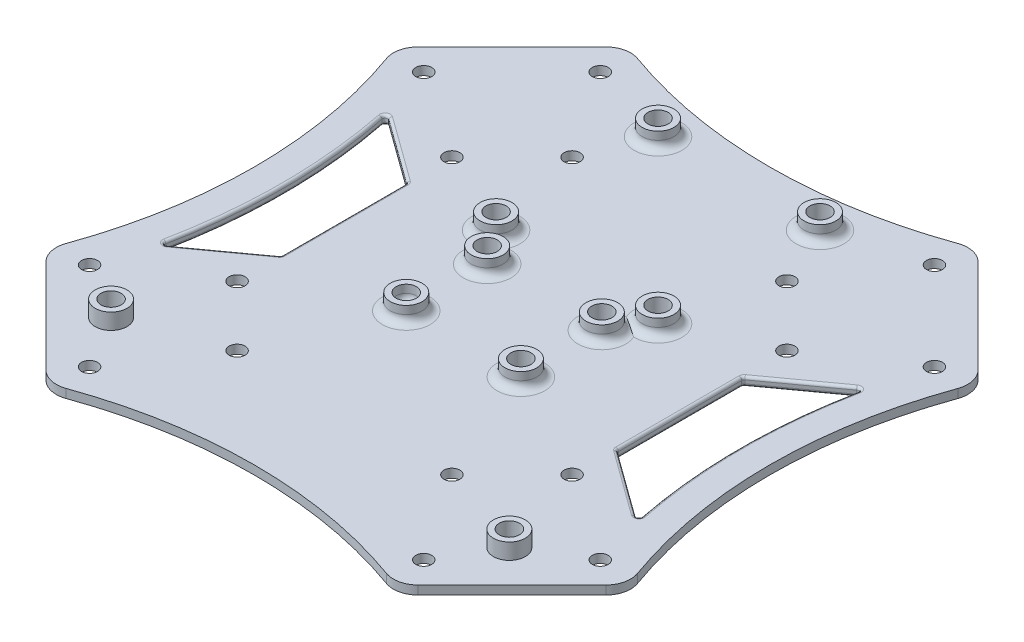
SolidWorks part; units mm, degrees
material "PLA"
ref_plane "Front Plane" through (0, 0, 0) normal (0, 0, 1) x (1, 0, 0)
ref_plane "Top Plane" through (0, 0, 0) normal (0, 1, 0) x (1, 0, 0)
ref_plane "Right Plane" through (0, 0, 0) normal (1, 0, 0) x (0, 0, -1)
sketch "Sketch1" plane through (0, 0, 0) normal (0, 1, 0) x (1, 0, 0)
  line L0 (-48.55, 0) -> (48.55, 0) construction
  line L1 (0, 48.55) -> (0, -48.55) construction
  line L2 (-30.1605, 53.8) -> (30.1605, 53.8) construction
  line L3 (0, 48.55) -> (0, 53.8) construction
  line L4 (-53.8, 30.1605) -> (-53.8, -30.1605) construction
  line L5 (-30.1605, -53.8) -> (30.1605, -53.8) construction
  line L6 (53.8, -30.1605) -> (53.8, 30.1605) construction
  line L7 (35.0464, 52.7056) -> (52.7056, 35.0464)
  line L8 (-52.7056, 35.0464) -> (-35.0464, 52.7056)
  line L9 (-52.7056, -35.0464) -> (-35.0464, -52.7056)
  line L10 (35.0464, -52.7056) -> (52.7056, -35.0464)
  line L11 (-43.876, -43.876) -> (43.876, 43.876) construction
  line L12 (-43.876, 43.876) -> (43.876, -43.876) construction
  line L13 (-31.7403, 54.075) -> (-31.7403, -54.075) construction
  line L14 (-31.7403, -54.075) -> (31.7403, -54.075) construction
  arc A0 (-30.1605, 53.8) -> (30.1605, 53.8) centre (0, 137.8088) ccw
  arc A1 (53.8, 30.1605) -> (53.8, -30.1605) centre (137.8088, 0) ccw
  arc A2 (30.1605, -53.8) -> (-30.1605, -53.8) centre (0, -137.8088) ccw
  arc A3 (-53.8, -30.1605) -> (-53.8, 30.1605) centre (-137.8088, 0) ccw
  arc A4 (-53.8, -30.1605) -> (-52.7056, -35.0464) centre (-49.3995, -31.7403) ccw
  arc A5 (-35.0464, -52.7056) -> (-30.1605, -53.8) centre (-31.7403, -49.3995) ccw
  arc A6 (30.1605, -53.8) -> (35.0464, -52.7056) centre (31.7403, -49.3995) ccw
  arc A7 (52.7056, -35.0464) -> (53.8, -30.1605) centre (49.3995, -31.7403) ccw
  arc A8 (53.8, 30.1605) -> (52.7056, 35.0464) centre (49.3995, 31.7403) ccw
  arc A9 (35.0464, 52.7056) -> (30.1605, 53.8) centre (31.7403, 49.3995) ccw
  arc A10 (-30.1605, 53.8) -> (-35.0464, 52.7056) centre (-31.7403, 49.3995) ccw
  arc A11 (-52.7056, 35.0464) -> (-53.8, 30.1605) centre (-49.3995, 31.7403) ccw
  point P2 (0, 0)
  point P6 (0, 0)
  point P34 (0, 0)
  dimension "D2" = 108.15
  dimension "D4" = 124.1
  dimension "D1" = 97.1
  dimension "D3" = 5.25
  dimension "D5" = 45
extrude "Boss-Extrude1" add sketch "Sketch1" along normal blind 0.825 and the other way blind 0.825
sketch "Sketch2" plane through (0, 0.825, 0) normal (0, 1, 0) x (1, 0, 0)
  line L0 (0, 30) -> (0, -30) construction
  line L1 (0, 40) -> (0, 30) construction
  line L2 (0, -30) -> (0, -40) construction
  line L3 (-15, 35) -> (15, 35) construction
  line L4 (15, 39) -> (15, 31)
  line L5 (-15, 39) -> (-15, 31)
  line L6 (-14, 40) -> (14, 40)
  line L7 (-14, 30) -> (14, 30)
  line L8 (-15, -35) -> (15, -35) construction
  line L9 (-15, -31) -> (-15, -39)
  line L10 (15, -31) -> (15, -39)
  line L11 (-14, -30) -> (14, -30)
  line L12 (-14, -40) -> (14, -40)
  line L13 (-18, 0) -> (18, 0) construction
  line L14 (-18, 0) -> (-27, 0) construction
  line L15 (18, 0) -> (27, 0) construction
  line L16 (-22.5, 9.5) -> (-22.5, -9.5) construction
  line L17 (22.5, 9.5) -> (22.5, -9.5) construction
  line L18 (-27, -9.5) -> (-27, 9.5)
  line L19 (-18, -9.5) -> (-18, 9.5)
  line L20 (18, -9.5) -> (18, 9.5)
  line L21 (27, -9.5) -> (27, 9.5)
  line L22 (-35, 0) -> (-27, 0) construction
  line L23 (-41, 0) -> (-35, 0) construction
  line L24 (27, 0) -> (35, 0) construction
  line L25 (35, 0) -> (41, 0) construction
  line L26 (-35, 11) -> (-35, -11)
  line L27 (-41, 11) -> (-41, -11)
  line L28 (-38, 11) -> (-38, -11) construction
  line L29 (35, 11) -> (35, -11)
  line L30 (41, 11) -> (41, -11)
  line L31 (38, 11) -> (38, -11) construction
  arc A0 (-14, 40) -> (-15, 39) centre (-14, 39) ccw
  arc A1 (15, 39) -> (14, 40) centre (14, 39) ccw
  arc A2 (-15, 31) -> (-14, 30) centre (-14, 31) ccw
  arc A3 (14, 30) -> (15, 31) centre (14, 31) ccw
  arc A4 (-14, -30) -> (-15, -31) centre (-14, -31) ccw
  arc A5 (15, -31) -> (14, -30) centre (14, -31) ccw
  arc A6 (14, -40) -> (15, -39) centre (14, -39) ccw
  arc A7 (-15, -39) -> (-14, -40) centre (-14, -39) ccw
  arc A8 (27, 9.5) -> (18, 9.5) centre (22.5, 9.5) ccw
  arc A9 (18, -9.5) -> (27, -9.5) centre (22.5, -9.5) ccw
  arc A10 (-27, -9.5) -> (-18, -9.5) centre (-22.5, -9.5) ccw
  arc A11 (-18, 9.5) -> (-27, 9.5) centre (-22.5, 9.5) ccw
  arc A12 (-35, 11) -> (-41, 11) centre (-38, 11) ccw
  arc A13 (-41, -11) -> (-35, -11) centre (-38, -11) ccw
  arc A14 (41, 11) -> (35, 11) centre (38, 11) ccw
  arc A15 (35, -11) -> (41, -11) centre (38, -11) ccw
  point P5 (0, 35)
  point P22 (0, -35)
  point P34 (-22.5, 0)
  point P36 (0, 0)
  point P45 (22.5, 0)
  point P64 (-38, 0)
  point P69 (38, 0)
  dimension "D6" = 30
  dimension "D8" = 36
  dimension "D13" = 8
  dimension "D18" = 22
  dimension "D1" = 60
  dimension "D2" = 10
  dimension "D3" = 10
  dimension "D4" = 30
  dimension "D5" = 8
  dimension "D7" = 8
  dimension "D9" = 9
  dimension "D10" = 9
  dimension "D11" = 19
  dimension "D12" = 19
  dimension "D14" = 8
  dimension "D15" = 6
  dimension "D16" = 6
  dimension "D17" = 22
extrude "Cut-Extrude1" [suppressed] cut sketch "Sketch2" against normal up to surface (1.65 mm away)
sketch "Sketch3" plane through (0, 0.825, 0) normal (0, 1, 0) x (1, 0, 0)
  line L0 (-48.0833, -31.4663) -> (-31.4663, -48.0833) construction
  line L1 (-52.7056, -35.0464) -> (-35.0464, -52.7056) construction
  line L2 (-39.7748, -39.7748) -> (-43.876, -43.876) construction
  line L3 (43.876, -43.876) -> (39.7748, -39.7748) construction
  line L4 (31.4663, -48.0833) -> (48.0833, -31.4663) construction
  line L5 (43.876, 43.876) -> (39.7748, 39.7748) construction
  line L6 (31.4663, 48.0833) -> (48.0833, 31.4663) construction
  line L7 (-43.876, 43.876) -> (-39.7748, 39.7748) construction
  line L8 (-31.4663, 48.0833) -> (-48.0833, 31.4663) construction
  line L9 (-35.0464, 52.7056) -> (-52.7056, 35.0464) construction
  line L10 (52.7056, 35.0464) -> (35.0464, 52.7056) construction
  line L11 (35.0464, -52.7056) -> (52.7056, -35.0464) construction
  line L12 (-31.5403, -20.2266) -> (-20.2266, -31.5403) construction
  line L13 (31.5403, -20.2266) -> (20.2266, -31.5403) construction
  line L14 (-31.5403, 20.2266) -> (-20.2266, 31.5403) construction
  line L15 (20.2266, 31.5403) -> (31.5403, 20.2266) construction
  line L16 (-25.8834, -25.8834) -> (-39.7748, -39.7748) construction
  line L17 (-39.7748, 39.7748) -> (-25.8834, 25.8834) construction
  line L18 (39.7748, 39.7748) -> (25.8834, 25.8834) construction
  line L19 (25.8834, -25.8834) -> (39.7748, -39.7748) construction
  line L20 (-20.2266, -31.5403) -> (-31.4663, -48.0833) construction
  line L21 (-31.5403, -20.2266) -> (-48.0833, -31.4663) construction
  circle A0 centre (-48.0833, -31.4663) radius 1.5
  circle A1 centre (-31.4663, -48.0833) radius 1.5
  circle A2 centre (31.4663, -48.0833) radius 1.5
  circle A3 centre (48.0833, -31.4663) radius 1.5
  circle A4 centre (48.0833, 31.4663) radius 1.5
  circle A5 centre (31.4663, 48.0833) radius 1.5
  circle A6 centre (-31.4663, 48.0833) radius 1.5
  circle A7 centre (-48.0833, 31.4663) radius 1.5
  circle A8 centre (-31.5403, -20.2266) radius 1.5
  circle A9 centre (-20.2266, -31.5403) radius 1.5
  circle A10 centre (-31.5403, 20.2266) radius 1.5
  circle A11 centre (-20.2266, 31.5403) radius 1.5
  circle A12 centre (20.2266, 31.5403) radius 1.5
  circle A13 centre (31.5403, 20.2266) radius 1.5
  circle A14 centre (31.5403, -20.2266) radius 1.5
  circle A15 centre (20.2266, -31.5403) radius 1.5
  dimension "D3" = 3
  dimension "D4" = 20
  dimension "D1" = 23.5
  dimension "D2" = 5.8
  dimension "D5" = 16
extrude "Cut-Extrude2" cut sketch "Sketch3" against normal up to surface (1.65 mm away) up to face at (0, -0.825, 0)
sketch "Sketch4" [suppressed] plane through (0, 0.825, 0) normal (0, 1, 0) x (1, 0, 0)
  line L0 (15.25, -39) -> (15.25, -31)
  line L1 (-15.25, -39) -> (-15.25, -31)
  line L2 (-14, -29.75) -> (14, -29.75)
  line L3 (-14, -40.25) -> (14, -40.25)
  line L4 (15, -39) -> (15, -31) construction
  line L5 (17.05, -39) -> (17.05, -31)
  line L6 (-14, -27.95) -> (14, -27.95)
  line L7 (-17.05, -39) -> (-17.05, -31)
  line L8 (-14, -42.05) -> (14, -42.05)
  line L9 (-14, 29.75) -> (14, 29.75)
  line L10 (-15.25, 31) -> (-15.25, 39)
  line L11 (-14, 40.25) -> (14, 40.25)
  line L12 (15.25, 39) -> (15.25, 31)
  line L13 (15, 31) -> (15, 39) construction
  line L14 (17.05, 39) -> (17.05, 31)
  line L15 (-14, 27.95) -> (14, 27.95)
  line L16 (-17.05, 31) -> (-17.05, 39)
  line L17 (-14, 42.05) -> (14, 42.05)
  line L18 (34.8696, -52.5288) -> (52.5288, -34.8696)
  line L19 (35.0464, -52.7056) -> (52.7056, -35.0464) construction
  line L20 (34.8696, 52.5288) -> (52.5288, 34.8696)
  line L21 (52.7056, 35.0464) -> (35.0464, 52.7056) construction
  line L22 (-52.5288, 34.8696) -> (-34.8696, 52.5288)
  line L23 (-35.0464, 52.7056) -> (-52.7056, 35.0464) construction
  line L24 (-52.5288, -34.8696) -> (-34.8696, -52.5288)
  line L25 (-52.7056, -35.0464) -> (-35.0464, -52.7056) construction
  line L26 (-51.256, 33.5968) -> (-33.5968, 51.256)
  line L27 (33.5968, 51.256) -> (51.256, 33.5968)
  line L28 (33.5968, -51.256) -> (51.256, -33.5968)
  line L29 (-51.256, -33.5968) -> (-33.5968, -51.256)
  line L30 (-31.4663, -45.8333) -> (-31.4663, -46.5833) construction
  line L31 (-29.5177, -46.9583) -> (-31.4663, -45.8333) construction
  line L32 (-31.4663, -45.8333) -> (-33.4148, -46.9583) construction
  line L33 (-33.4148, -46.9583) -> (-33.4148, -49.2083) construction
  line L34 (-33.4148, -49.2083) -> (-31.4663, -50.3333) construction
  line L35 (-31.4663, -50.3333) -> (-29.5177, -49.2083) construction
  line L36 (-29.5177, -49.2083) -> (-29.5177, -46.9583) construction
  line L37 (-31.4663, -45.8333) -> (-31.4663, -45.0833) construction
  line L39 (-48.0833, -29.2163) -> (-50.0318, -30.3413) construction
  line L40 (-50.0318, -30.3413) -> (-50.0318, -32.5913) construction
  line L41 (-50.0318, -32.5913) -> (-48.0833, -33.7163) construction
  line L42 (-48.0833, -33.7163) -> (-46.1347, -32.5913) construction
  line L43 (-46.1347, -32.5913) -> (-46.1347, -30.3413) construction
  line L44 (-46.1347, -30.3413) -> (-48.0833, -29.2163) construction
  line L45 (-31.5403, -17.9766) -> (-33.4888, -19.1016) construction
  line L46 (-33.4888, -19.1016) -> (-33.4888, -21.3516) construction
  line L47 (-33.4888, -21.3516) -> (-31.5403, -22.4766) construction
  line L48 (-31.5403, -22.4766) -> (-29.5917, -21.3516) construction
  line L49 (-29.5917, -21.3516) -> (-29.5917, -19.1016) construction
  line L50 (-29.5917, -19.1016) -> (-31.5403, -17.9766) construction
  line L51 (-20.2266, -29.2903) -> (-22.1751, -30.4153) construction
  line L52 (-22.1751, -30.4153) -> (-22.1751, -32.6653) construction
  line L53 (-22.1751, -32.6653) -> (-20.2266, -33.7903) construction
  line L54 (-20.2266, -33.7903) -> (-18.278, -32.6653) construction
  line L55 (-18.278, -32.6653) -> (-18.278, -30.4153) construction
  line L56 (-18.278, -30.4153) -> (-20.2266, -29.2903) construction
  line L57 (20.2266, 33.7903) -> (18.278, 32.6653) construction
  line L58 (18.278, 32.6653) -> (18.278, 30.4153) construction
  line L59 (18.278, 30.4153) -> (20.2266, 29.2903) construction
  line L60 (20.2266, 29.2903) -> (22.1751, 30.4153) construction
  line L61 (22.1751, 30.4153) -> (22.1751, 32.6653) construction
  line L62 (22.1751, 32.6653) -> (20.2266, 33.7903) construction
  line L63 (31.5403, 22.4766) -> (29.5917, 21.3516) construction
  line L64 (29.5917, 21.3516) -> (29.5917, 19.1016) construction
  line L65 (29.5917, 19.1016) -> (31.5403, 17.9766) construction
  line L66 (31.5403, 17.9766) -> (33.4888, 19.1016) construction
  line L67 (33.4888, 19.1016) -> (33.4888, 21.3516) construction
  line L68 (33.4888, 21.3516) -> (31.5403, 22.4766) construction
  line L69 (48.0833, 33.7163) -> (46.1347, 32.5913) construction
  line L70 (46.1347, 32.5913) -> (46.1347, 30.3413) construction
  line L71 (46.1347, 30.3413) -> (48.0833, 29.2163) construction
  line L72 (48.0833, 29.2163) -> (50.0318, 30.3413) construction
  line L73 (50.0318, 30.3413) -> (50.0318, 32.5913) construction
  line L74 (50.0318, 32.5913) -> (48.0833, 33.7163) construction
  line L75 (31.4663, 50.3333) -> (29.5177, 49.2083) construction
  line L76 (29.5177, 49.2083) -> (29.5177, 46.9583) construction
  line L77 (29.5177, 46.9583) -> (31.4663, 45.8333) construction
  line L78 (31.4663, 45.8333) -> (33.4148, 46.9583) construction
  line L79 (33.4148, 46.9583) -> (33.4148, 49.2083) construction
  line L80 (33.4148, 49.2083) -> (31.4663, 50.3333) construction
  line L81 (-50.3333, 31.4663) -> (-49.2083, 29.5177) construction
  line L82 (-49.2083, 29.5177) -> (-46.9583, 29.5177) construction
  line L83 (-46.9583, 29.5177) -> (-45.8333, 31.4663) construction
  line L84 (-45.8333, 31.4663) -> (-46.9583, 33.4148) construction
  line L85 (-46.9583, 33.4148) -> (-49.2083, 33.4148) construction
  line L86 (-49.2083, 33.4148) -> (-50.3333, 31.4663) construction
  line L87 (-33.7903, 20.2266) -> (-32.6653, 18.278) construction
  line L88 (-32.6653, 18.278) -> (-30.4153, 18.278) construction
  line L89 (-30.4153, 18.278) -> (-29.2903, 20.2266) construction
  line L90 (-29.2903, 20.2266) -> (-30.4153, 22.1751) construction
  line L91 (-30.4153, 22.1751) -> (-32.6653, 22.1751) construction
  line L92 (-32.6653, 22.1751) -> (-33.7903, 20.2266) construction
  line L93 (-22.4766, 31.5403) -> (-21.3516, 29.5917) construction
  line L94 (-21.3516, 29.5917) -> (-19.1016, 29.5917) construction
  line L95 (-19.1016, 29.5917) -> (-17.9766, 31.5403) construction
  line L96 (-17.9766, 31.5403) -> (-19.1016, 33.4888) construction
  line L97 (-19.1016, 33.4888) -> (-21.3516, 33.4888) construction
  line L98 (-21.3516, 33.4888) -> (-22.4766, 31.5403) construction
  line L99 (-29.2163, 48.0833) -> (-30.3413, 50.0318) construction
  line L100 (-30.3413, 50.0318) -> (-32.5913, 50.0318) construction
  line L101 (-32.5913, 50.0318) -> (-33.7163, 48.0833) construction
  line L102 (-33.7163, 48.0833) -> (-32.5913, 46.1347) construction
  line L103 (-32.5913, 46.1347) -> (-30.3413, 46.1347) construction
  line L104 (-30.3413, 46.1347) -> (-29.2163, 48.0833) construction
  line L105 (22.4766, -31.5403) -> (21.3516, -29.5917) construction
  line L106 (21.3516, -29.5917) -> (19.1016, -29.5917) construction
  line L107 (19.1016, -29.5917) -> (17.9766, -31.5403) construction
  line L108 (17.9766, -31.5403) -> (19.1016, -33.4888) construction
  line L109 (19.1016, -33.4888) -> (21.3516, -33.4888) construction
  line L110 (21.3516, -33.4888) -> (22.4766, -31.5403) construction
  line L111 (33.7903, -20.2266) -> (32.6653, -18.278) construction
  line L112 (32.6653, -18.278) -> (30.4153, -18.278) construction
  line L113 (30.4153, -18.278) -> (29.2903, -20.2266) construction
  line L114 (29.2903, -20.2266) -> (30.4153, -22.1751) construction
  line L115 (30.4153, -22.1751) -> (32.6653, -22.1751) construction
  line L116 (32.6653, -22.1751) -> (33.7903, -20.2266) construction
  line L117 (33.7163, -48.0833) -> (32.5913, -46.1347) construction
  line L118 (32.5913, -46.1347) -> (30.3413, -46.1347) construction
  line L119 (30.3413, -46.1347) -> (29.2163, -48.0833) construction
  line L120 (29.2163, -48.0833) -> (30.3413, -50.0318) construction
  line L121 (30.3413, -50.0318) -> (32.5913, -50.0318) construction
  line L122 (32.5913, -50.0318) -> (33.7163, -48.0833) construction
  line L123 (50.3333, -31.4663) -> (49.2083, -29.5177) construction
  line L124 (49.2083, -29.5177) -> (46.9583, -29.5177) construction
  line L125 (46.9583, -29.5177) -> (45.8333, -31.4663) construction
  line L126 (45.8333, -31.4663) -> (46.9583, -33.4148) construction
  line L127 (46.9583, -33.4148) -> (49.2083, -33.4148) construction
  line L128 (49.2083, -33.4148) -> (50.3333, -31.4663) construction
  arc A0 (-14, -29.75) -> (-15.25, -31) centre (-14, -31) ccw
  arc A1 (15.25, -31) -> (14, -29.75) centre (14, -31) ccw
  arc A2 (-15.25, -39) -> (-14, -40.25) centre (-14, -39) ccw
  arc A3 (14, -40.25) -> (15.25, -39) centre (14, -39) ccw
  arc A4 (14, -40) -> (15, -39) centre (14, -39) ccw construction
  arc A5 (15, -31) -> (14, -30) centre (14, -31) ccw construction
  arc A6 (-14, -30) -> (-15, -31) centre (-14, -31) ccw construction
  arc A7 (-15, -39) -> (-14, -40) centre (-14, -39) ccw construction
  arc A8 (17.05, -31) -> (14, -27.95) centre (14, -31) ccw
  arc A9 (-14, -27.95) -> (-17.05, -31) centre (-14, -31) ccw
  arc A10 (-17.05, -39) -> (-14, -42.05) centre (-14, -39) ccw
  arc A11 (14, -42.05) -> (17.05, -39) centre (14, -39) ccw
  arc A12 (-15.25, 31) -> (-14, 29.75) centre (-14, 31) ccw
  arc A13 (-14, 40.25) -> (-15.25, 39) centre (-14, 39) ccw
  arc A14 (15.25, 39) -> (14, 40.25) centre (14, 39) ccw
  arc A15 (14, 29.75) -> (15.25, 31) centre (14, 31) ccw
  arc A16 (14, 30) -> (15, 31) centre (14, 31) ccw construction
  arc A17 (15, 39) -> (14, 40) centre (14, 39) ccw construction
  arc A18 (-14, 40) -> (-15, 39) centre (-14, 39) ccw construction
  arc A19 (-15, 31) -> (-14, 30) centre (-14, 31) ccw construction
  arc A20 (14, 27.95) -> (17.05, 31) centre (14, 31) ccw
  arc A21 (-17.05, 31) -> (-14, 27.95) centre (-14, 31) ccw
  arc A22 (-14, 42.05) -> (-17.05, 39) centre (-14, 39) ccw
  arc A23 (17.05, 39) -> (14, 42.05) centre (14, 39) ccw
  arc A24 (30.245, -53.5647) -> (-30.245, -53.5647) centre (0, -137.8088) ccw
  arc A25 (30.1605, -53.8) -> (-30.1605, -53.8) centre (0, -137.8088) ccw construction
  arc A26 (-53.5647, -30.245) -> (-53.5647, 30.245) centre (-137.8088, 0) ccw
  arc A27 (-30.245, 53.5647) -> (30.245, 53.5647) centre (0, 137.8088) ccw
  arc A28 (53.5647, 30.245) -> (53.5647, -30.245) centre (137.8088, 0) ccw
  arc A29 (53.8, 30.1605) -> (53.8, -30.1605) centre (137.8088, 0) ccw construction
  arc A30 (-30.1605, 53.8) -> (30.1605, 53.8) centre (0, 137.8088) ccw construction
  arc A31 (-53.8, -30.1605) -> (-53.8, 30.1605) centre (-137.8088, 0) ccw construction
  arc A32 (34.8696, 52.5288) -> (30.245, 53.5647) centre (31.7403, 49.3995) ccw
  arc A33 (35.0464, 52.7056) -> (30.1605, 53.8) centre (31.7403, 49.3995) ccw construction
  arc A34 (53.5647, 30.245) -> (52.5288, 34.8696) centre (49.3995, 31.7403) ccw
  arc A35 (53.8, 30.1605) -> (52.7056, 35.0464) centre (49.3995, 31.7403) ccw construction
  arc A36 (52.5288, -34.8696) -> (53.5647, -30.245) centre (49.3995, -31.7403) ccw
  arc A37 (52.7056, -35.0464) -> (53.8, -30.1605) centre (49.3995, -31.7403) ccw construction
  arc A38 (30.245, -53.5647) -> (34.8696, -52.5288) centre (31.7403, -49.3995) ccw
  arc A39 (30.1605, -53.8) -> (35.0464, -52.7056) centre (31.7403, -49.3995) ccw construction
  arc A40 (-34.8696, -52.5288) -> (-30.245, -53.5647) centre (-31.7403, -49.3995) ccw
  arc A41 (-35.0464, -52.7056) -> (-30.1605, -53.8) centre (-31.7403, -49.3995) ccw construction
  arc A42 (-53.5647, -30.245) -> (-52.5288, -34.8696) centre (-49.3995, -31.7403) ccw
  arc A43 (-53.8, -30.1605) -> (-52.7056, -35.0464) centre (-49.3995, -31.7403) ccw construction
  arc A44 (-52.5288, 34.8696) -> (-53.5647, 30.245) centre (-49.3995, 31.7403) ccw
  arc A45 (-52.7056, 35.0464) -> (-53.8, 30.1605) centre (-49.3995, 31.7403) ccw construction
  arc A46 (-30.245, 53.5647) -> (-34.8696, 52.5288) centre (-31.7403, 49.3995) ccw
  arc A47 (-30.1605, 53.8) -> (-35.0464, 52.7056) centre (-31.7403, 49.3995) ccw construction
  arc A48 (-51.8706, -30.8532) -> (-51.8706, 30.8532) centre (-137.8088, 0) ccw
  arc A49 (-51.256, 33.5968) -> (-51.8706, 30.8532) centre (-49.3995, 31.7403) ccw
  arc A50 (-30.8532, 51.8706) -> (-33.5968, 51.256) centre (-31.7403, 49.3995) ccw
  arc A51 (-30.8532, 51.8706) -> (30.8532, 51.8706) centre (0, 137.8088) ccw
  arc A52 (33.5968, 51.256) -> (30.8532, 51.8706) centre (31.7403, 49.3995) ccw
  arc A53 (51.8706, 30.8532) -> (51.256, 33.5968) centre (49.3995, 31.7403) ccw
  arc A54 (51.8706, 30.8532) -> (51.8706, -30.8532) centre (137.8088, 0) ccw
  arc A55 (51.256, -33.5968) -> (51.8706, -30.8532) centre (49.3995, -31.7403) ccw
  arc A56 (30.8532, -51.8706) -> (33.5968, -51.256) centre (31.7403, -49.3995) ccw
  arc A57 (30.8532, -51.8706) -> (-30.8532, -51.8706) centre (0, -137.8088) ccw
  arc A58 (-33.5968, -51.256) -> (-30.8532, -51.8706) centre (-31.7403, -49.3995) ccw
  arc A59 (-51.8706, -30.8532) -> (-51.256, -33.5968) centre (-49.3995, -31.7403) ccw
  circle A60 centre (-31.4663, -48.0833) radius 3
  circle A61 centre (-48.0833, -31.4663) radius 3
  circle A62 centre (-31.5403, -20.2266) radius 3
  circle A63 centre (-20.2266, -31.5403) radius 3
  circle A64 centre (-48.0833, 31.4663) radius 3
  circle A65 centre (-31.5403, 20.2266) radius 3
  circle A66 centre (-20.2266, 31.5403) radius 3
  circle A67 centre (-31.4663, 48.0833) radius 3
  circle A68 centre (20.2266, 31.5403) radius 3
  circle A69 centre (31.4663, 48.0833) radius 3
  circle A70 centre (48.0833, 31.4663) radius 3
  circle A71 centre (31.5403, 20.2266) radius 3
  circle A72 centre (20.2266, -31.5403) radius 3
  circle A73 centre (31.5403, -20.2266) radius 3
  circle A74 centre (48.0833, -31.4663) radius 3
  circle A75 centre (31.4663, -48.0833) radius 3
  circle A76 centre (-31.4663, -48.0833) radius 1.5 construction
  circle A77 centre (-48.0833, -31.4663) radius 1.5 construction
  circle A78 centre (-31.5403, -20.2266) radius 1.5 construction
  circle A79 centre (-20.2266, -31.5403) radius 1.5 construction
  circle A80 centre (20.2266, -31.5403) radius 1.5 construction
  circle A81 centre (31.4663, -48.0833) radius 1.5 construction
  circle A82 centre (48.0833, -31.4663) radius 1.5 construction
  circle A83 centre (31.5403, -20.2266) radius 1.5 construction
  circle A84 centre (48.0833, 31.4663) radius 1.5 construction
  circle A85 centre (31.5403, 20.2266) radius 1.5 construction
  circle A86 centre (20.2266, 31.5403) radius 1.5 construction
  circle A87 centre (31.4663, 48.0833) radius 1.5 construction
  circle A88 centre (-20.2266, 31.5403) radius 1.5 construction
  circle A89 centre (-31.5403, 20.2266) radius 1.5 construction
  circle A90 centre (-48.0833, 31.4663) radius 1.5 construction
  circle A91 centre (-31.4663, 48.0833) radius 1.5 construction
  circle A92 centre (-48.0833, -31.4663) radius 1.5
  circle A93 centre (-31.4663, -48.0833) radius 1.5
  circle A94 centre (-20.2266, -31.5403) radius 1.5
  circle A95 centre (-31.5403, -20.2266) radius 1.5
  circle A96 centre (-48.0833, 31.4663) radius 1.5
  circle A97 centre (-31.5403, 20.2266) radius 1.5
  circle A98 centre (-20.2266, 31.5403) radius 1.5
  circle A99 centre (-31.4663, 48.0833) radius 1.5
  circle A100 centre (20.2266, 31.5403) radius 1.5
  circle A101 centre (31.4663, 48.0833) radius 1.5
  circle A102 centre (48.0833, 31.4663) radius 1.5
  circle A103 centre (31.5403, 20.2266) radius 1.5
  circle A104 centre (31.5403, -20.2266) radius 1.5
  circle A105 centre (20.2266, -31.5403) radius 1.5
  circle A106 centre (48.0833, -31.4663) radius 1.5
  circle A107 centre (31.4663, -48.0833) radius 1.5
  circle A108 centre (-31.4663, -48.0833) radius 1.9486 construction
  circle A109 centre (-48.0833, -31.4663) radius 1.9486 construction
  circle A110 centre (-31.5403, -20.2266) radius 1.9486 construction
  circle A111 centre (-20.2266, -31.5403) radius 1.9486 construction
  circle A112 centre (-31.4663, -50.3333) radius 0.25
  circle A113 centre (-29.5177, -49.2083) radius 0.25
  circle A114 centre (-29.5177, -46.9583) radius 0.25
  circle A115 centre (-31.4663, -45.8333) radius 0.25
  circle A116 centre (-33.4148, -46.9583) radius 0.25
  circle A117 centre (-33.4148, -49.2083) radius 0.25
  circle A118 centre (-48.0833, -33.7163) radius 0.25
  circle A119 centre (-46.1347, -32.5913) radius 0.25
  circle A120 centre (-46.1347, -30.3413) radius 0.25
  circle A121 centre (-48.0833, -29.2163) radius 0.25
  circle A122 centre (-50.0318, -30.3413) radius 0.25
  circle A123 centre (-50.0318, -32.5913) radius 0.25
  circle A124 centre (-31.5403, -22.4766) radius 0.25
  circle A125 centre (-29.5917, -21.3516) radius 0.25
  circle A126 centre (-29.5917, -19.1016) radius 0.25
  circle A127 centre (-31.5403, -17.9766) radius 0.25
  circle A128 centre (-33.4888, -19.1016) radius 0.25
  circle A129 centre (-33.4888, -21.3516) radius 0.25
  circle A130 centre (-20.2266, -33.7903) radius 0.25
  circle A131 centre (-18.278, -32.6653) radius 0.25
  circle A132 centre (-18.278, -30.4153) radius 0.25
  circle A133 centre (-20.2266, -29.2903) radius 0.25
  circle A134 centre (-22.1751, -30.4153) radius 0.25
  circle A135 centre (-22.1751, -32.6653) radius 0.25
  circle A136 centre (20.2266, 31.5403) radius 1.9486 construction
  circle A137 centre (31.5403, 20.2266) radius 1.9486 construction
  circle A138 centre (48.0833, 31.4663) radius 1.9486 construction
  circle A139 centre (31.4663, 48.0833) radius 1.9486 construction
  circle A140 centre (20.2266, 29.2903) radius 0.25
  circle A141 centre (22.1751, 30.4153) radius 0.25
  circle A142 centre (22.1751, 32.6653) radius 0.25
  circle A143 centre (18.278, 30.4153) radius 0.25
  circle A144 centre (18.278, 32.6653) radius 0.25
  circle A145 centre (20.2266, 33.7903) radius 0.25
  circle A146 centre (31.4663, 45.8333) radius 0.25
  circle A147 centre (29.5177, 46.9583) radius 0.25
  circle A148 centre (29.5177, 49.2083) radius 0.25
  circle A149 centre (31.4663, 50.3333) radius 0.25
  circle A150 centre (33.4148, 49.2083) radius 0.25
  circle A151 centre (33.4148, 46.9583) radius 0.25
  circle A152 centre (29.5917, 21.3516) radius 0.25
  circle A153 centre (29.5917, 19.1016) radius 0.25
  circle A154 centre (31.5403, 17.9766) radius 0.25
  circle A155 centre (33.4888, 19.1016) radius 0.25
  circle A156 centre (33.4888, 21.3516) radius 0.25
  circle A157 centre (31.5403, 22.4766) radius 0.25
  circle A158 centre (48.0833, 29.2163) radius 0.25
  circle A159 centre (46.1347, 30.3413) radius 0.25
  circle A160 centre (50.0318, 30.3413) radius 0.25
  circle A161 centre (50.0318, 32.5913) radius 0.25
  circle A162 centre (48.0833, 33.7163) radius 0.25
  circle A163 centre (46.1347, 32.5913) radius 0.25
  circle A164 centre (-48.0833, 31.4663) radius 1.9486 construction
  circle A165 centre (-31.5403, 20.2266) radius 1.9486 construction
  circle A166 centre (-20.2266, 31.5403) radius 1.9486 construction
  circle A167 centre (-31.4663, 48.0833) radius 1.9486 construction
  circle A168 centre (-46.9583, 29.5177) radius 0.25
  circle A169 centre (-45.8333, 31.4663) radius 0.25
  circle A170 centre (-46.9583, 33.4148) radius 0.25
  circle A171 centre (-49.2083, 33.4148) radius 0.25
  circle A172 centre (-50.3333, 31.4663) radius 0.25
  circle A173 centre (-49.2083, 29.5177) radius 0.25
  circle A174 centre (-32.6653, 18.278) radius 0.25
  circle A175 centre (-33.7903, 20.2266) radius 0.25
  circle A176 centre (-32.6653, 22.1751) radius 0.25
  circle A177 centre (-30.4153, 22.1751) radius 0.25
  circle A178 centre (-29.2903, 20.2266) radius 0.25
  circle A179 centre (-30.4153, 18.278) radius 0.25
  circle A180 centre (-19.1016, 29.5917) radius 0.25
  circle A181 centre (-21.3516, 29.5917) radius 0.25
  circle A182 centre (-22.4766, 31.5403) radius 0.25
  circle A183 centre (-21.3516, 33.4888) radius 0.25
  circle A184 centre (-19.1016, 33.4888) radius 0.25
  circle A185 centre (-17.9766, 31.5403) radius 0.25
  circle A186 centre (-32.5913, 46.1347) radius 0.25
  circle A187 centre (-33.7163, 48.0833) radius 0.25
  circle A188 centre (-32.5913, 50.0318) radius 0.25
  circle A189 centre (-30.3413, 50.0318) radius 0.25
  circle A190 centre (-29.2163, 48.0833) radius 0.25
  circle A191 centre (-30.3413, 46.1347) radius 0.25
  circle A192 centre (20.2266, -31.5403) radius 1.9486 construction
  circle A193 centre (31.5403, -20.2266) radius 1.9486 construction
  circle A194 centre (31.4663, -48.0833) radius 1.9486 construction
  circle A195 centre (48.0833, -31.4663) radius 1.9486 construction
  circle A196 centre (19.1016, -33.4888) radius 0.25
  circle A197 centre (21.3516, -33.4888) radius 0.25
  circle A198 centre (22.4766, -31.5403) radius 0.25
  circle A199 centre (21.3516, -29.5917) radius 0.25
  circle A200 centre (19.1016, -29.5917) radius 0.25
  circle A201 centre (17.9766, -31.5403) radius 0.25
  circle A202 centre (30.3413, -50.0318) radius 0.25
  circle A203 centre (29.2163, -48.0833) radius 0.25
  circle A204 centre (30.3413, -46.1347) radius 0.25
  circle A205 centre (32.5913, -46.1347) radius 0.25
  circle A206 centre (33.7163, -48.0833) radius 0.25
  circle A207 centre (32.5913, -50.0318) radius 0.25
  circle A208 centre (46.9583, -33.4148) radius 0.25
  circle A209 centre (45.8333, -31.4663) radius 0.25
  circle A210 centre (46.9583, -29.5177) radius 0.25
  circle A211 centre (49.2083, -29.5177) radius 0.25
  circle A212 centre (50.3333, -31.4663) radius 0.25
  circle A213 centre (49.2083, -33.4148) radius 0.25
  circle A214 centre (30.4153, -22.1751) radius 0.25
  circle A215 centre (29.2903, -20.2266) radius 0.25
  circle A216 centre (30.4153, -18.278) radius 0.25
  circle A217 centre (32.6653, -18.278) radius 0.25
  circle A218 centre (33.7903, -20.2266) radius 0.25
  circle A219 centre (32.6653, -22.1751) radius 0.25
  dimension "D1" = 0.25
  dimension "D3" = 0.25
  dimension "D5" = 0.25
  dimension "D7" = 6
  dimension "D8" = 0.5
  dimension "D2" = 1.8
  dimension "D4" = 1.8
  dimension "D6" = 1.8
extrude "Boss-Extrude2" [suppressed] add sketch "Sketch4" along normal blind 0.001 contours A27 A46 L22 A44 A26 A42 L24 A40 A24 A38 L18 A36 A28 A34 L20 A32 A59 A48 A49 L26 A50 A51 A52 L27 A53 A54 A55 L28 A56 A57 A58 L29 | L8 A11 L5 A8 L6 A9 L7 A10 A3 L3 A2 L1 A0 L2 A1 L0 | L14 A23 L17 A22 L16 A21 L15 A20 A15 L9 A12 L10 A13 L11 A14 L12 | A61 A92 | A60 A93 | A63 A94 | A62 A95 | A75 A107 | A72 A105 | A73 A104 | A74 A106 | A71 A103 | A70 A102 | A68 A100 | A69 A101 | A64 A96 | A65 A97 | A66 A98 | A67 A99
mirror "Mirror2" [suppressed] about plane through (0, 0, 0) normal (0, 1, 0)
sketch "Sketch5" [suppressed] plane through (0, 0.825, 0) normal (0, 1, 0) x (1, 0, 0)
  circle A0 centre (-31.4663, -45.8333) radius 0.25
  circle A1 centre (-29.5177, -46.9583) radius 0.25
  circle A2 centre (-29.5177, -49.2083) radius 0.25
  circle A3 centre (-31.4663, -50.3333) radius 0.25
  circle A4 centre (-33.4148, -49.2083) radius 0.25
  circle A5 centre (-33.4148, -46.9583) radius 0.25
  circle A6 centre (-48.0833, -33.7163) radius 0.25
  circle A7 centre (-50.0318, -32.5913) radius 0.25
  circle A8 centre (-50.0318, -30.3413) radius 0.25
  circle A9 centre (-48.0833, -29.2163) radius 0.25
  circle A10 centre (-46.1347, -30.3413) radius 0.25
  circle A11 centre (-46.1347, -32.5913) radius 0.25
  circle A12 centre (-33.4888, -21.3516) radius 0.25
  circle A13 centre (-33.4888, -19.1016) radius 0.25
  circle A14 centre (-31.5403, -17.9766) radius 0.25
  circle A15 centre (-29.5917, -19.1016) radius 0.25
  circle A16 centre (-29.5917, -21.3516) radius 0.25
  circle A17 centre (-31.5403, -22.4766) radius 0.25
  circle A18 centre (-22.1751, -30.4153) radius 0.25
  circle A19 centre (-22.1751, -32.6653) radius 0.25
  circle A20 centre (-20.2266, -33.7903) radius 0.25
  circle A21 centre (-18.278, -32.6653) radius 0.25
  circle A22 centre (-18.278, -30.4153) radius 0.25
  circle A23 centre (-20.2266, -29.2903) radius 0.25
  circle A24 centre (-31.4663, -50.3333) radius 0.25 construction
  circle A25 centre (-33.4148, -49.2083) radius 0.25 construction
  circle A26 centre (-33.4148, -46.9583) radius 0.25 construction
  circle A27 centre (-31.4663, -45.8333) radius 0.25 construction
  circle A28 centre (-29.5177, -46.9583) radius 0.25 construction
  circle A29 centre (-29.5177, -49.2083) radius 0.25 construction
  circle A30 centre (-48.0833, -33.7163) radius 0.25 construction
  circle A31 centre (-50.0318, -32.5913) radius 0.25 construction
  circle A32 centre (-50.0318, -30.3413) radius 0.25 construction
  circle A33 centre (-48.0833, -29.2163) radius 0.25 construction
  circle A34 centre (-46.1347, -30.3413) radius 0.25 construction
  circle A35 centre (-46.1347, -32.5913) radius 0.25 construction
  circle A36 centre (-31.5403, -22.4766) radius 0.25 construction
  circle A37 centre (-33.4888, -21.3516) radius 0.25 construction
  circle A38 centre (-33.4888, -19.1016) radius 0.25 construction
  circle A39 centre (-31.5403, -17.9766) radius 0.25 construction
  circle A40 centre (-29.5917, -19.1016) radius 0.25 construction
  circle A41 centre (-29.5917, -21.3516) radius 0.25 construction
  circle A42 centre (-22.1751, -32.6653) radius 0.25 construction
  circle A43 centre (-22.1751, -30.4153) radius 0.25 construction
  circle A44 centre (-20.2266, -29.2903) radius 0.25 construction
  circle A45 centre (-18.278, -30.4153) radius 0.25 construction
  circle A46 centre (-18.278, -32.6653) radius 0.25 construction
  circle A47 centre (-20.2266, -33.7903) radius 0.25 construction
  circle A48 centre (19.1016, -33.4888) radius 0.25
  circle A49 centre (17.9766, -31.5403) radius 0.25
  circle A50 centre (19.1016, -29.5917) radius 0.25
  circle A51 centre (21.3516, -29.5917) radius 0.25
  circle A52 centre (22.4766, -31.5403) radius 0.25
  circle A53 centre (21.3516, -33.4888) radius 0.25
  circle A54 centre (19.1016, -33.4888) radius 0.25 construction
  circle A55 centre (21.3516, -33.4888) radius 0.25 construction
  circle A56 centre (17.9766, -31.5403) radius 0.25 construction
  circle A57 centre (19.1016, -29.5917) radius 0.25 construction
  circle A58 centre (21.3516, -29.5917) radius 0.25 construction
  circle A59 centre (22.4766, -31.5403) radius 0.25 construction
  circle A60 centre (29.2903, -20.2266) radius 0.25
  circle A61 centre (30.4153, -18.278) radius 0.25
  circle A62 centre (32.6653, -18.278) radius 0.25
  circle A63 centre (30.4153, -22.1751) radius 0.25
  circle A64 centre (32.6653, -22.1751) radius 0.25
  circle A65 centre (33.7903, -20.2266) radius 0.25
  circle A66 centre (29.2903, -20.2266) radius 0.25 construction
  circle A67 centre (30.4153, -18.278) radius 0.25 construction
  circle A68 centre (32.6653, -18.278) radius 0.25 construction
  circle A69 centre (30.4153, -22.1751) radius 0.25 construction
  circle A70 centre (32.6653, -22.1751) radius 0.25 construction
  circle A71 centre (33.7903, -20.2266) radius 0.25 construction
  circle A72 centre (46.9583, -29.5177) radius 0.25
  circle A73 centre (49.2083, -29.5177) radius 0.25
  circle A74 centre (45.8333, -31.4663) radius 0.25
  circle A75 centre (46.9583, -33.4148) radius 0.25
  circle A76 centre (49.2083, -33.4148) radius 0.25
  circle A77 centre (50.3333, -31.4663) radius 0.25
  circle A78 centre (45.8333, -31.4663) radius 0.25 construction
  circle A79 centre (46.9583, -29.5177) radius 0.25 construction
  circle A80 centre (49.2083, -29.5177) radius 0.25 construction
  circle A81 centre (50.3333, -31.4663) radius 0.25 construction
  circle A82 centre (49.2083, -33.4148) radius 0.25 construction
  circle A83 centre (46.9583, -33.4148) radius 0.25 construction
  circle A84 centre (30.3413, -46.1347) radius 0.25
  circle A85 centre (32.5913, -46.1347) radius 0.25
  circle A86 centre (29.2163, -48.0833) radius 0.25
  circle A87 centre (30.3413, -50.0318) radius 0.25
  circle A88 centre (32.5913, -50.0318) radius 0.25
  circle A89 centre (33.7163, -48.0833) radius 0.25
  circle A90 centre (29.2163, -48.0833) radius 0.25 construction
  circle A91 centre (30.3413, -46.1347) radius 0.25 construction
  circle A92 centre (32.5913, -46.1347) radius 0.25 construction
  circle A93 centre (30.3413, -50.0318) radius 0.25 construction
  circle A94 centre (32.5913, -50.0318) radius 0.25 construction
  circle A95 centre (33.7163, -48.0833) radius 0.25 construction
  circle A96 centre (-32.6653, 18.278) radius 0.25
  circle A97 centre (-33.7903, 20.2266) radius 0.25
  circle A98 centre (-32.6653, 22.1751) radius 0.25
  circle A99 centre (-30.4153, 22.1751) radius 0.25
  circle A100 centre (-29.2903, 20.2266) radius 0.25
  circle A101 centre (-30.4153, 18.278) radius 0.25
  circle A102 centre (-32.6653, 18.278) radius 0.25 construction
  circle A103 centre (-33.7903, 20.2266) radius 0.25 construction
  circle A104 centre (-32.6653, 22.1751) radius 0.25 construction
  circle A105 centre (-30.4153, 22.1751) radius 0.25 construction
  circle A106 centre (-29.2903, 20.2266) radius 0.25 construction
  circle A107 centre (-30.4153, 18.278) radius 0.25 construction
  circle A108 centre (-49.2083, 29.5177) radius 0.25
  circle A109 centre (-50.3333, 31.4663) radius 0.25
  circle A110 centre (-49.2083, 33.4148) radius 0.25
  circle A111 centre (-46.9583, 33.4148) radius 0.25
  circle A112 centre (-45.8333, 31.4663) radius 0.25
  circle A113 centre (-46.9583, 29.5177) radius 0.25
  circle A114 centre (-49.2083, 29.5177) radius 0.25 construction
  circle A115 centre (-50.3333, 31.4663) radius 0.25 construction
  circle A116 centre (-49.2083, 33.4148) radius 0.25 construction
  circle A117 centre (-46.9583, 33.4148) radius 0.25 construction
  circle A118 centre (-45.8333, 31.4663) radius 0.25 construction
  circle A119 centre (-46.9583, 29.5177) radius 0.25 construction
  circle A120 centre (-32.5913, 46.1347) radius 0.25
  circle A121 centre (-33.7163, 48.0833) radius 0.25
  circle A122 centre (-32.5913, 50.0318) radius 0.25
  circle A123 centre (-30.3413, 50.0318) radius 0.25
  circle A124 centre (-29.2163, 48.0833) radius 0.25
  circle A125 centre (-30.3413, 46.1347) radius 0.25
  circle A126 centre (-32.5913, 46.1347) radius 0.25 construction
  circle A127 centre (-33.7163, 48.0833) radius 0.25 construction
  circle A128 centre (-32.5913, 50.0318) radius 0.25 construction
  circle A129 centre (-30.3413, 50.0318) radius 0.25 construction
  circle A130 centre (-29.2163, 48.0833) radius 0.25 construction
  circle A131 centre (-30.3413, 46.1347) radius 0.25 construction
  circle A132 centre (-21.3516, 29.5917) radius 0.25
  circle A133 centre (-22.4766, 31.5403) radius 0.25
  circle A134 centre (-21.3516, 33.4888) radius 0.25
  circle A135 centre (-19.1016, 33.4888) radius 0.25
  circle A136 centre (-17.9766, 31.5403) radius 0.25
  circle A137 centre (-19.1016, 29.5917) radius 0.25
  circle A138 centre (-21.3516, 29.5917) radius 0.25 construction
  circle A139 centre (-22.4766, 31.5403) radius 0.25 construction
  circle A140 centre (-21.3516, 33.4888) radius 0.25 construction
  circle A141 centre (-19.1016, 33.4888) radius 0.25 construction
  circle A142 centre (-17.9766, 31.5403) radius 0.25 construction
  circle A143 centre (-19.1016, 29.5917) radius 0.25 construction
  circle A144 centre (20.2266, 29.2903) radius 0.25
  circle A145 centre (18.278, 30.4153) radius 0.25
  circle A146 centre (18.278, 32.6653) radius 0.25
  circle A147 centre (20.2266, 33.7903) radius 0.25
  circle A148 centre (22.1751, 32.6653) radius 0.25
  circle A149 centre (22.1751, 30.4153) radius 0.25
  circle A150 centre (20.2266, 29.2903) radius 0.25 construction
  circle A151 centre (18.278, 30.4153) radius 0.25 construction
  circle A152 centre (18.278, 32.6653) radius 0.25 construction
  circle A153 centre (20.2266, 33.7903) radius 0.25 construction
  circle A154 centre (22.1751, 32.6653) radius 0.25 construction
  circle A155 centre (22.1751, 30.4153) radius 0.25 construction
  circle A156 centre (29.5917, 21.3516) radius 0.25
  circle A157 centre (31.5403, 22.4766) radius 0.25
  circle A158 centre (29.5917, 19.1016) radius 0.25
  circle A159 centre (31.5403, 17.9766) radius 0.25
  circle A160 centre (33.4888, 19.1016) radius 0.25
  circle A161 centre (33.4888, 21.3516) radius 0.25
  circle A162 centre (29.5917, 21.3516) radius 0.25 construction
  circle A163 centre (29.5917, 19.1016) radius 0.25 construction
  circle A164 centre (31.5403, 22.4766) radius 0.25 construction
  circle A165 centre (31.5403, 17.9766) radius 0.25 construction
  circle A166 centre (33.4888, 19.1016) radius 0.25 construction
  circle A167 centre (33.4888, 21.3516) radius 0.25 construction
  circle A168 centre (48.0833, 29.2163) radius 0.25
  circle A169 centre (50.0318, 30.3413) radius 0.25
  circle A170 centre (50.0318, 32.5913) radius 0.25
  circle A171 centre (48.0833, 33.7163) radius 0.25
  circle A172 centre (46.1347, 32.5913) radius 0.25
  circle A173 centre (46.1347, 30.3413) radius 0.25
  circle A174 centre (46.1347, 30.3413) radius 0.25 construction
  circle A175 centre (48.0833, 29.2163) radius 0.25 construction
  circle A176 centre (50.0318, 30.3413) radius 0.25 construction
  circle A177 centre (50.0318, 32.5913) radius 0.25 construction
  circle A178 centre (48.0833, 33.7163) radius 0.25 construction
  circle A179 centre (46.1347, 32.5913) radius 0.25 construction
  circle A180 centre (31.4663, 45.8333) radius 0.25
  circle A181 centre (29.5177, 46.9583) radius 0.25
  circle A182 centre (29.5177, 49.2083) radius 0.25
  circle A183 centre (31.4663, 50.3333) radius 0.25
  circle A184 centre (33.4148, 49.2083) radius 0.25
  circle A185 centre (33.4148, 46.9583) radius 0.25
  circle A186 centre (31.4663, 45.8333) radius 0.25 construction
  circle A187 centre (29.5177, 46.9583) radius 0.25 construction
  circle A188 centre (29.5177, 49.2083) radius 0.25 construction
  circle A189 centre (31.4663, 50.3333) radius 0.25 construction
  circle A190 centre (33.4148, 49.2083) radius 0.25 construction
  circle A191 centre (33.4148, 46.9583) radius 0.25 construction
extrude "Cut-Extrude3" [suppressed] cut sketch "Sketch5" against normal up to surface (1.65 mm away)
sketch "Sketch7" plane through (0, -0.825, 0) normal (0, -1, 0) x (1, 0, 0)
  circle A0 centre (8.76, 21.225) radius 1
  circle A1 centre (8.76, 21.225) radius 3
  dimension "D1" = 2
  dimension "D2" = 2
extrude "Boss-Extrude3" [suppressed] add sketch "Sketch7" along normal up to surface (5 mm away)
mirror "Mirror5" [suppressed] about plane through (0, 0, 0) normal (0, 0, 1) second plane through (0, 0, 0) second plane normal (1, 0, 0)
fillet "Fillet2" [suppressed] radius 2
sketch "Sketch9" [suppressed] plane through (0, -0.825, 0) normal (0, -1, 0) x (1, 0, 0)
  line L0 (20, -33.5) -> (20, 33.5)
  line L1 (15, -28.5) -> (-15, -28.5) construction
  line L2 (15, -28.5) -> (15, 28.5) construction
  line L3 (15, 28.5) -> (-15, 28.5) construction
  line L4 (-15, -28.5) -> (-15, 28.5) construction
  line L5 (15, -28.5) -> (-15, 28.5) construction
  line L6 (15, 28.5) -> (-15, -28.5) construction
  line L7 (17, -30.5) -> (-17, -30.5)
  line L8 (17, -30.5) -> (17, 30.5)
  line L9 (17, 30.5) -> (-17, 30.5)
  line L10 (-17, -30.5) -> (-17, 30.5)
  line L11 (17, -30.5) -> (-17, 30.5) construction
  line L12 (17, 30.5) -> (-17, -30.5) construction
  line L13 (20, 33.5) -> (-20, 33.5)
  line L14 (-20, -33.5) -> (-20, 33.5)
  line L15 (20, -33.5) -> (-20, -33.5)
  point P0 (0, 0)
  point P6 (0, 0)
  dimension "D1" = 30
  dimension "D2" = 57
  dimension "D3" = 2
  dimension "D4" = 2
  dimension "D5" = 3
extrude "Boss-Extrude4" [suppressed] add sketch "Sketch9" along normal blind 15
sketch "Sketch12" [suppressed] plane through (0, -15.825, 0) normal (0, -1, 0) x (1, 0, 0)
  line L4 (-20, -33.5) -> (20, -33.5)
  line L5 (20, -33.5) -> (20, 33.5)
  line L6 (20, 33.5) -> (-20, 33.5)
  line L7 (-20, 33.5) -> (-20, -33.5)
  line L8 (-20, -33.5) -> (20, -33.5)
  line L9 (20, -33.5) -> (20, 33.5)
  line L10 (20, 33.5) -> (-20, 33.5)
  line L11 (-20, 33.5) -> (-20, -33.5)
  dimension "D1" = 0
extrude "Boss-Extrude5" [suppressed] add sketch "Sketch12" against normal blind 3
sketch "Sketch13" [suppressed] plane through (0, -15.825, 0) normal (0, -1, 0) x (1, 0, 0)
  line L0 (0, 0) -> (70.1434, 0) construction
  line L1 (-20, -33.5) -> (-8, -33.5)
  line L2 (-20, -33.5) -> (-20, -8)
  line L3 (-20, -8) -> (-8, -8)
  line L4 (-8, -33.5) -> (-8, -8)
  line L5 (0, 0) -> (0, 8) construction
  line L6 (-20, 8) -> (-8, 8)
  line L8 (-20, 33.5) -> (-8, 33.5)
  line L9 (-20, 33.5) -> (-20, 8)
  line L10 (20, 33.5) -> (20, 8)
  line L11 (20, 33.5) -> (8, 33.5)
  line L13 (20, 8) -> (8, 8)
  line L14 (20, -8) -> (8, -8)
  line L15 (8, -33.5) -> (8, -8)
  line L16 (20, -33.5) -> (8, -33.5)
  line L17 (20, -33.5) -> (20, -8)
  line L18 (-8, 8) -> (8, 8)
  line L19 (8, 33.5) -> (-8, 33.5)
  line L20 (0, 33.5) -> (0, 78.4079) construction
  dimension "D1" = 8
  dimension "D2" = 8
extrude "Cut-Extrude4" [suppressed] cut sketch "Sketch13" against normal up to surface (15 mm away)
fillet "Fillet3" [suppressed] radius 5
fillet "Fillet4" [suppressed] radius 3
sketch "Sketch14" plane through (0, -0.825, 0) normal (0, -1, 0) x (1, 0, 0)
  line L0 (11.0616, 33.1861) -> (-8.9384, 33.1861)
  line L1 (11.0616, 33.1861) -> (11.0616, 43.1861)
  line L2 (-8.9384, 33.1861) -> (-8.9384, 43.1861)
  line L3 (11.0616, 43.1861) -> (-8.9384, 43.1861)
  line L4 (11.0616, 33.1861) -> (-8.9384, 43.1861) construction
  line L5 (-8.9384, 33.1861) -> (11.0616, 43.1861) construction
  line L6 (33.1861, -11.0616) -> (33.1861, 8.9384)
  line L7 (33.1861, -11.0616) -> (43.1861, -11.0616)
  line L8 (33.1861, 8.9384) -> (43.1861, 8.9384)
  line L9 (43.1861, -11.0616) -> (43.1861, 8.9384)
  line L10 (33.1861, -11.0616) -> (43.1861, 8.9384) construction
  line L11 (33.1861, 8.9384) -> (43.1861, -11.0616) construction
  line L12 (-11.0616, -33.1861) -> (8.9384, -33.1861)
  line L13 (-11.0616, -33.1861) -> (-11.0616, -43.1861)
  line L14 (8.9384, -33.1861) -> (8.9384, -43.1861)
  line L15 (-11.0616, -43.1861) -> (8.9384, -43.1861)
  line L16 (-11.0616, -33.1861) -> (8.9384, -43.1861) construction
  line L17 (8.9384, -33.1861) -> (-11.0616, -43.1861) construction
  line L18 (-33.1861, 11.0616) -> (-33.1861, -8.9384)
  line L19 (-33.1861, 11.0616) -> (-43.1861, 11.0616)
  line L20 (-33.1861, -8.9384) -> (-43.1861, -8.9384)
  line L21 (-43.1861, 11.0616) -> (-43.1861, -8.9384)
  line L22 (-33.1861, 11.0616) -> (-43.1861, -8.9384) construction
  line L23 (-33.1861, -8.9384) -> (-43.1861, 11.0616) construction
  point P1 (1.0616, 38.1861)
  point P8 (38.1861, -1.0616)
  point P13 (-1.0616, -38.1861)
  point P18 (-38.1861, 1.0616)
  point P23 (0, 0)
  dimension "D2" = 10
  dimension "D3" = 20
  dimension "D1" = 4
extrude "Boss-Extrude6" [suppressed] add sketch "Sketch14" along normal blind 12
sketch "Sketch15" [suppressed] plane through (0, 0, -43.1861) normal (0, 0, -1) x (-1, 0, 0)
  circle A0 centre (0, -5.9948) radius 4.7602
extrude "Cut-Extrude5" [suppressed] cut sketch "Sketch15" against normal through all both and the other way through all
sketch "Sketch16" plane through (0, 0.825, 0) normal (0, 1, 0) x (1, 0, 0)
  line L0 (-10.795, 6.12) -> (10.795, 6.12) construction
  line L1 (15, 12.5) -> (-15.5, 12.5) construction
  line L2 (15, 12.5) -> (15, 43) construction
  line L3 (15, 43) -> (-15.5, 43) construction
  line L4 (-15.5, 12.5) -> (-15.5, 43) construction
  line L5 (15, 12.5) -> (-15.5, 43) construction
  line L6 (15, 43) -> (-15.5, 12.5) construction
  line L7 (-10.795, -9.12) -> (10.795, -9.12) construction
  line L8 (-10.795, 6.12) -> (-10.795, -9.12) construction
  line L11 (10.795, 6.12) -> (10.795, -9.12) construction
  line L13 (15, 25) -> (15, -25) construction
  line L14 (-10.795, -9.12) -> (10.795, 6.12) construction
  line L15 (10.795, -9.12) -> (0, -1.5) construction
  line L16 (0, -1.5) -> (-10.795, 6.12) construction
  line L17 (0, -1.5) -> (0, 0) construction
  line L18 (-37.5, -38) -> (37.5, -38) construction
  line L19 (0, 0) -> (0, -38) construction
  circle A0 centre (-15.5, 43) radius 1.9
  circle A1 centre (15, 43) radius 1.9
  circle A2 centre (15, 12.5) radius 1.9
  circle A3 centre (-15.5, 12.5) radius 1.9
  circle A4 centre (-15.5, 43) radius 3
  circle A5 centre (15, 43) radius 3
  circle A6 centre (15, 12.5) radius 3
  circle A7 centre (-15.5, 12.5) radius 3
  circle A8 centre (10.795, 6.12) radius 1.9
  circle A9 centre (10.795, 6.12) radius 3
  circle A10 centre (-10.795, 6.12) radius 1.9
  circle A11 centre (-10.795, 6.12) radius 3
  circle A12 centre (10.795, -9.12) radius 1.9
  circle A13 centre (10.795, -9.12) radius 3
  circle A14 centre (-10.795, -9.12) radius 1.9
  circle A15 centre (-10.795, -9.12) radius 3
  circle A16 centre (-37.5, -38) radius 1.9
  circle A17 centre (-37.5, -38) radius 3
  circle A18 centre (37.5, -38) radius 1.9
  circle A19 centre (37.5, -38) radius 3
  point P41 (-0.25, 27.75)
  dimension "D3" = 3.8
  dimension "D4" = 6
  dimension "D7" = 15.24
  dimension "D8" = 3.8
  dimension "D9" = 6
  dimension "D1" = 30.5
  dimension "D2" = 30.5
  dimension "D5" = 12.5
  dimension "D6" = 21.59
  dimension "D10" = 1.5
  dimension "D11" = 75
  dimension "D12" = 38
extrude "Boss-Extrude7" add sketch "Sketch16" along normal blind 3
fillet "Fillet5" radius 1.5 9 edges at (-15.5, 0.825, -9.5) (15, 0.825, -9.5) (15, 0.825, -40) (-15.5, 0.825, -40) (-10.795, 0.825, 12.12) (-10.795, 0.825, 11.02) (10.795, 0.825, 12.12) (10.795, 0.825, -3.12) (-10.795, 0.825, -3.12)
sketch "Sketch18" plane through (0, 0.825, 0) normal (0, 1, 0) x (1, 0, 0)
  line L0 (31.6441, 11.8592) -> (31.6441, -11.8592)
  line L1 (31.6441, -11.8592) -> (45.0963, -21.606)
  line L2 (31.6441, 11.8592) -> (45.0963, 21.606)
  line L3 (0, -44.5349) -> (0, 44.5349) construction
  line L4 (-31.6441, 11.8592) -> (-45.0963, 21.606)
  line L5 (-31.6441, -11.8592) -> (-45.0963, -21.606)
  line L6 (-31.6441, 11.8592) -> (-31.6441, -11.8592)
  arc A0 (45.0963, 21.606) -> (45.0963, -21.606) centre (146.8334, 0) ccw
  arc A1 (-45.0963, 21.606) -> (-45.0963, -21.606) centre (-146.8334, 0) cw
  point P2 (31.6441, 0)
extrude "Cut-Extrude6" cut sketch "Sketch18" against normal through all
fillet "Fillet6" radius 0.5 24 edges at (-42.8274, -0.825, 0) (-42.8274, 0.825, 0) (-38.3702, -0.825, -16.7326) (-45.0963, 0, -21.606) (-38.3702, 0.825, -16.7326) (-31.6441, -0.825, 0) (-31.6441, 0, -11.8592) (-31.6441, 0.825, 0) (-45.0963, 0, 21.606) (-38.3702, -0.825, 16.7326) (-31.6441, 0, 11.8592) (-38.3702, 0.825, 16.7326) (38.3702, -0.825, -16.7326) (38.3702, 0.825, -16.7326) (42.8274, -0.825, 0) (45.0963, 0, -21.606) (42.8274, 0.825, 0) (38.3702, -0.825, 16.7326) (45.0963, 0, 21.606) (38.3702, 0.825, 16.7326) (31.6441, 0, -11.8592) (31.6441, -0.825, 0) (31.6441, 0, 11.8592) (31.6441, 0.825, 0)
